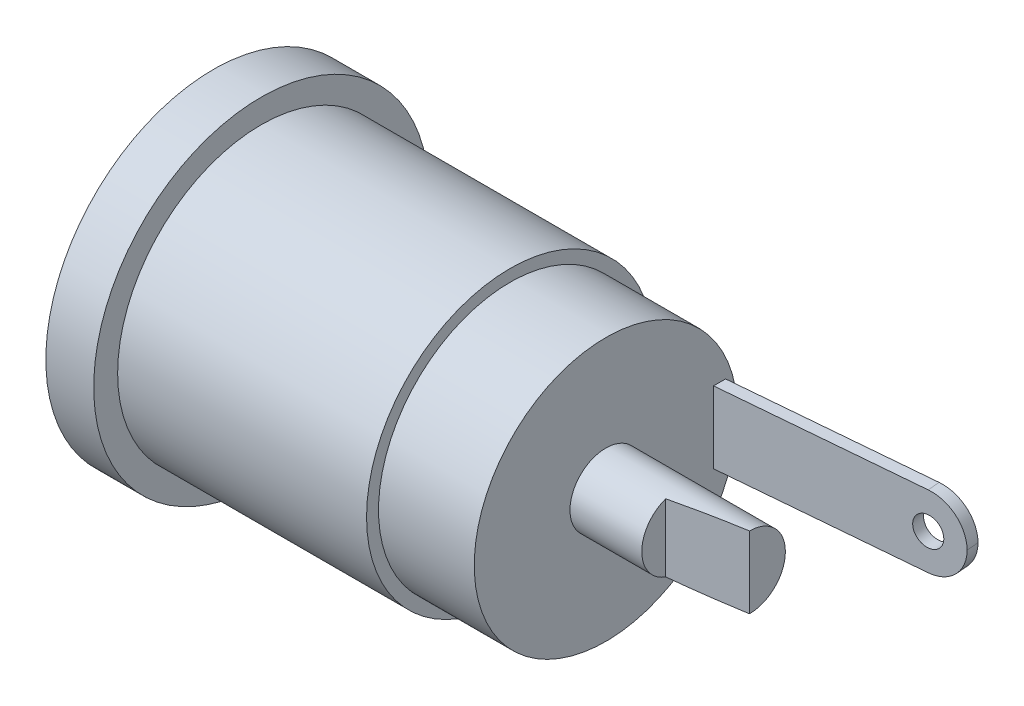
SolidWorks part; units mm, degrees
ref_plane "Front Plane" through (0, 0, 0) normal (0, 0, 1) x (1, 0, 0)
ref_plane "Top Plane" through (0, 0, 0) normal (0, 1, 0) x (1, 0, 0)
ref_plane "Right Plane" through (0, 0, 0) normal (1, 0, 0) x (0, 0, -1)
sketch "Sketch1" plane through (0, 0, 0) normal (0, 1, 0) x (1, 0, 0)
  line L0 (0, 0) -> (0, 7)
  line L1 (0, 7) -> (2, 7)
  line L2 (2, 7) -> (2, 6)
  line L3 (2, 6) -> (12.4, 6)
  line L4 (12.4, 6) -> (12.4, 5.5)
  line L5 (12.4, 5.5) -> (16.4, 5.5)
  line L6 (16.4, 5.5) -> (16.4, 0)
  line L7 (16.4, 0) -> (0, 0)
  point P8 (2, 3.145)
  point P10 (61.6773, 1.8038)
  point P11 (0, 3.5)
  point P12 (11.2107, 1.8903)
  dimension "D1" = 1
  dimension "D2" = 2
  dimension "D3" = 16.4
  dimension "D4" = 6
  dimension "D5" = 4
  dimension "D6" = 5.5
revolve "Revolve1" add sketch "Sketch1" angle 360 about L7
sketch "Sketch2" plane through (0, 0, 0) normal (-1, 0, 0) x (0, 0, 1)
  circle A0 centre (0, 0) radius 2.85
  dimension "D1" = 5.7
extrude "Cut-Extrude1" cut sketch "Sketch2" against normal blind 10
chamfer "Chamfer1" distance 1 angle 45 1 edges at (0, 0, 2.85)
sketch "Sketch4" plane through (16.4, 0, 0) normal (1, 0, 0) x (0, 0, -1)
  circle A0 centre (0, 0) radius 1.5
  dimension "D1" = 3
extrude "Boss-Extrude1" add sketch "Sketch4" along normal blind 6
sketch "Sketch5" plane through (0, 0, 0) normal (0, 1, 0) x (1, 0, 0)
  line L0 (22.4, -1.5) -> (19.4, -1.5)
  line L1 (16.4, -1.5) -> (22.4, -1.5) construction
  line L2 (19.4, -1.5) -> (19.4, -0.5)
  line L3 (19.4, -0.5) -> (22.4, 0)
  line L4 (22.4, -1.5) -> (22.4, 1.5) construction
  line L5 (22.4, 0) -> (22.4, -1.5)
  point P5 (0, 0)
  point P12 (19.4, -0.5183)
  dimension "D1" = 1
extrude "Cut-Extrude2" cut sketch "Sketch5" against normal through all both and the other way through all
sketch "Sketch6" plane through (0, 0, 0) normal (0, 1, 0) x (1, 0, 0)
  line L0 (16.4, 5) -> (26.1, 5.8486)
  line L1 (16.4, -5.5) -> (16.4, 5.5) construction
  line L2 (26.1, 5.8486) -> (26.1436, 5.3505)
  line L3 (26.1436, 5.3505) -> (16.4, 4.4981)
  line L4 (16.4, 4.4981) -> (16.4, 5)
  line L5 (16.4, 4.4981) -> (20.6419, 4.4981) construction
  line L6 (16.4, 5.5) -> (12.4, 5.5) construction
  point P7 (16.4, 5.0489)
  dimension "D1" = 9.7
  dimension "D2" = 0.5
  dimension "D3" = 5
  dimension "D4" = 0.5
extrude "Boss-Extrude2" add sketch "Sketch6" along normal mid plane 3
fillet "Fillet1" radius 1.5 2 edges at (26.1218, 1.5, -5.5996) (26.1218, -1.5, -5.5996)
sketch "Sketch7" plane through (-0.3095, 0, -3.5381) normal (-0.0872, 0, -0.9962) x (-0.9962, 0, 0.0872)
  circle A0 centre (-25.0104, 0) radius 0.6
  arc A1 (-25.0104, 1.5) -> (-26.5104, 0) centre (-25.0104, 0) ccw construction
  dimension "D1" = 1.2
extrude "Cut-Extrude3" cut sketch "Sketch7" against normal blind 3
